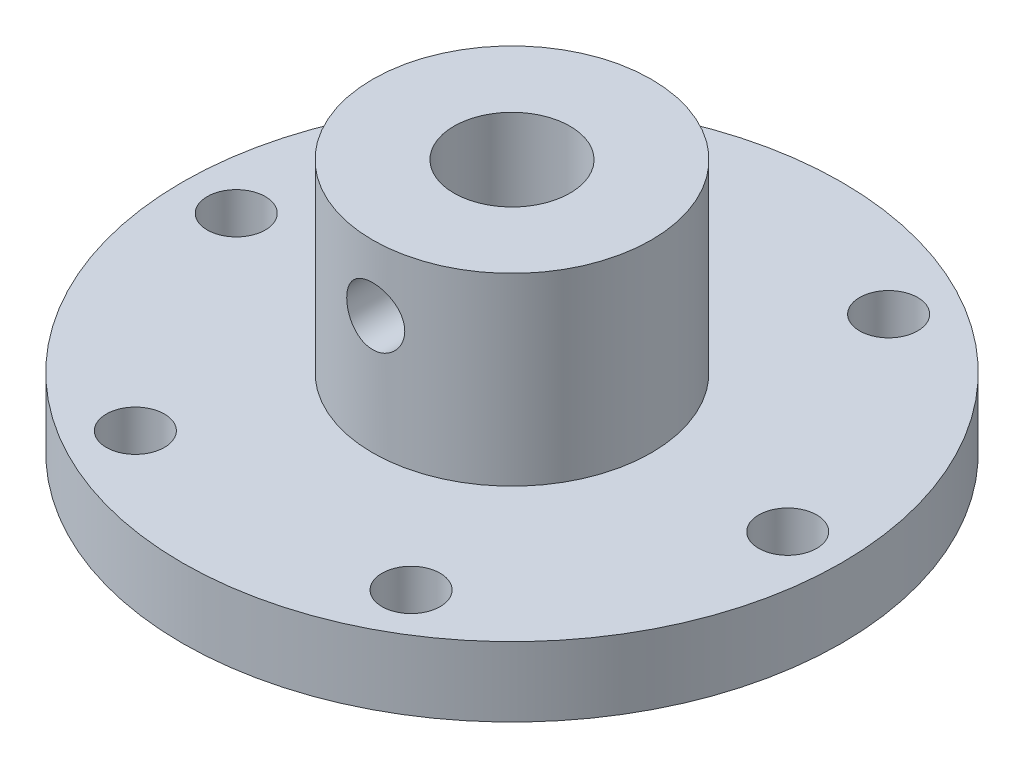
SolidWorks part; units mm, degrees
material "Plain Carbon Steel"
ref_plane "Front Plane" through (0, 0, 0) normal (0, 0, 1) x (1, 0, 0)
ref_plane "Top Plane" through (0, 0, 0) normal (0, 1, 0) x (1, 0, 0)
ref_plane "Right Plane" through (0, 0, 0) normal (1, 0, 0) x (0, 0, -1)
sketch "Sketch1" plane through (0, 0, 0) normal (0, 1, 0) x (1, 0, 0)
  circle A0 centre (0, 0) radius 28.4
  dimension "D1" = 56.8
extrude "Boss-Extrude1" add sketch "Sketch1" along normal blind 6
sketch "Sketch2" plane through (0, 6, 0) normal (0, 1, 0) x (1, 0, 0)
  circle A0 centre (0, 0) radius 12
  dimension "D1" = 24
extrude "Boss-Extrude2" add sketch "Sketch2" along normal blind 15.875
sketch "Sketch3" plane through (0, 21.875, 0) normal (0, 1, 0) x (1, 0, 0)
  circle A0 centre (0, 0) radius 5
  dimension "D1" = 10
extrude "Cut-Extrude1" cut sketch "Sketch3" against normal through all
sketch "Sketch4" plane through (0, 0, 0) normal (0, 0, 1) x (1, 0, 0)
  line L0 (0, 0) -> (0, 21.875) construction
  line L1 (5, 21.875) -> (-5, 21.875) construction
  circle A0 centre (0, 16.2) radius 3
  dimension "D1" = 6
  dimension "D3" = 16.2
hole_wizard "M6x1.0 Tapped Hole1" positions "Sketch5" profile "Sketch7" tap size "M6x1.0" standard "ANSI Metric" end condition through all
sketch "Sketch5" plane through (0, 0, 0) normal (0, 0, 1) x (1, 0, 0)
  point P0 (0, 16.2)
sketch "Sketch7" plane through (0, 16.2, 0) normal (1, 0, 0) x (0, 1, 0)
  line L0 (0, 0) -> (0, 28.4)
  line L1 (0, 28.4) -> (2.5, 28.4)
  line L2 (2.5, 28.4) -> (2.5, 0)
  line L5 (2.5, 0) -> (0, 0)
  line L11 (0, -6.35) -> (0, 107.95) construction
  dimension "Thru Tap Drill Dia." = 5
  dimension "Thru Tap Drill Depth" = 28.4
cosmetic thread "Hole Thread2" parameters "D2"=6
sketch "Sketch8" plane through (0, 0, 0) normal (0, -1, 0) x (1, 0, 0)
  circle A0 centre (0, 0) radius 23.75 construction
  circle A1 centre (-23.75, 0) radius 2.6
  circle A2 centre (-11.875, 20.5681) radius 2.6
  circle A3 centre (11.875, 20.5681) radius 2.6
  circle A4 centre (23.75, 0) radius 2.6
  circle A5 centre (11.875, -20.5681) radius 2.6
  circle A6 centre (-11.875, -20.5681) radius 2.6
  point P17 (0, 0)
  dimension "D1" = 47.5
  dimension "D2" = 5.2
  dimension "D3" = 6
hole_wizard "M6 Tapped Hole1" positions "Sketch9" profile "Sketch10" tap size "M6" standard "AS" end condition through all
sketch "Sketch9" plane through (0, 0, 0) normal (0, -1, 0) x (-1, 0, 0)
  point P0 (23.75, 0)
  point P3 (11.875, -20.5681)
  point P6 (-11.875, -20.5681)
  point P9 (-23.75, 0)
  point P12 (-11.875, 20.5681)
  point P15 (11.875, 20.5681)
sketch "Sketch10" plane through (-23.75, 0, 0) normal (1, 0, 0) x (0, 0, -1)
  line L0 (0, 0) -> (0, 21.875)
  line L1 (0, 21.875) -> (2.5, 21.875)
  line L2 (2.5, 21.875) -> (2.5, 0)
  line L5 (2.5, 0) -> (0, 0)
  line L11 (0, -6.35) -> (0, 107.95) construction
  dimension "Thru Tap Drill Dia." = 5
  dimension "Thru Tap Drill Depth" = 21.875
cosmetic thread "Hole Thread3" parameters "D2"=6
cosmetic thread "Hole Thread4" parameters "D2"=6
cosmetic thread "Hole Thread5" parameters "D2"=6
cosmetic thread "Hole Thread6" parameters "D2"=6
cosmetic thread "Hole Thread7" parameters "D2"=6
cosmetic thread "Hole Thread8" parameters "D2"=6
